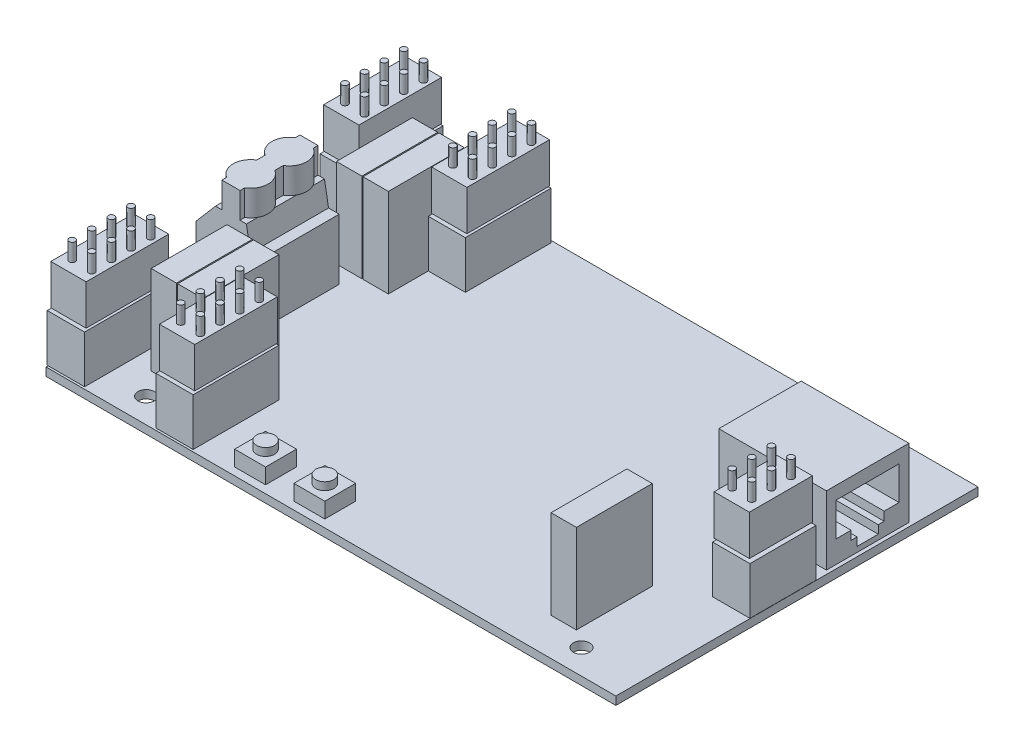
SolidWorks part; units mm, degrees
ref_plane "Front Plane" through (0, 0, 0) normal (0, 0, 1) x (1, 0, 0)
ref_plane "Top Plane" through (0, 0, 0) normal (0, 1, 0) x (1, 0, 0)
ref_plane "Right Plane" through (0, 0, 0) normal (1, 0, 0) x (0, 0, -1)
sketch "Sketch1" plane through (0, 0, 0) normal (0, 1, 0) x (1, 0, 0)
  line L0 (1.5775, 0) -> (0, 0) construction
  line L1 (-55.31, -35.15) -> (55.31, -35.15)
  line L2 (-55.31, -35.15) -> (-55.31, 35.15)
  line L3 (-55.31, 35.15) -> (55.31, 35.15)
  line L4 (55.31, -35.15) -> (55.31, 35.15)
  line L5 (-55.31, -35.15) -> (55.31, 35.15) construction
  line L6 (-55.31, 35.15) -> (55.31, -35.15) construction
  line L7 (-40.6725, -30.35) -> (43.8275, -30.35) construction
  line L8 (-40.6725, -30.35) -> (-40.6725, 30.35) construction
  line L9 (-40.6725, 30.35) -> (43.8275, 30.35) construction
  line L10 (43.8275, -30.35) -> (43.8275, 30.35) construction
  line L11 (-40.6725, -30.35) -> (43.8275, 30.35) construction
  line L12 (-40.6725, 30.35) -> (43.8275, -30.35) construction
  line L13 (-42.26, -30.35) -> (-55.31, -30.35) construction
  circle A0 centre (-40.6725, -30.35) radius 1.5875
  circle A1 centre (-40.6725, 30.35) radius 1.5875
  circle A2 centre (43.8275, 30.35) radius 1.5875
  circle A3 centre (43.8275, -30.35) radius 1.5875
  point P0 (0, 0)
  point P14 (0, 0)
  dimension "D3" = 3.175
  dimension "D6" = 4.8
  dimension "D7" = 70.3
  dimension "D1" = 13.05
  dimension "D2" = 110.62
  dimension "D4" = 84.5
  dimension "D5" = 60.7
extrude "Boss-Extrude1" add sketch "Sketch1" against normal blind 1.5875
sketch "Sketch2" plane through (0, 0, 0) normal (0, 1, 0) x (1, 0, 0)
  line L0 (-30.1535, -20.707) -> (-30.1535, -24.517) construction
  line L1 (-30.1535, -24.517) -> (-30.1535, -28.327) construction
  line L2 (-30.1535, -28.327) -> (-30.1535, -32.137) construction
  line L3 (51.0175, 1.137) -> (51.0175, -6.483) construction
  line L4 (51.0175, 1.137) -> (51.0175, -2.673) construction
  line L5 (-30.1535, 24.505) -> (-30.1535, 20.695) construction
  line L6 (-30.1535, 32.125) -> (-30.1535, 28.315) construction
  line L7 (-30.1535, 28.315) -> (-30.1535, 24.505) construction
  line L8 (-51.1085, 28.315) -> (-51.1085, 24.505) construction
  line L9 (-51.2355, -24.517) -> (-51.2355, -28.327) construction
  line L10 (-51.1085, 24.505) -> (-51.1085, 20.695) construction
  line L11 (-51.2355, -28.327) -> (-51.2355, -32.137) construction
  line L12 (-51.1085, 32.125) -> (-51.1085, 28.315) construction
  line L13 (-51.2355, -20.707) -> (-51.2355, -24.517) construction
  line L17 (55.31, 35.15) -> (-55.31, 35.15) construction
  line L19 (-55.1725, -34.55) -> (54.8275, -34.55) construction
  line L20 (-55.1725, -34.55) -> (-55.1725, 34.55) construction
  line L21 (-55.1725, 34.55) -> (54.8275, 34.55) construction
  line L22 (54.8275, -34.55) -> (54.8275, 34.55) construction
  circle A0 centre (51.0175, 1.137) radius 0.5
  circle A1 centre (51.0175, -2.673) radius 0.5
  circle A2 centre (51.0175, -6.483) radius 0.5
  circle A3 centre (-30.1535, -20.707) radius 0.5
  circle A4 centre (-30.1535, -24.517) radius 0.5
  circle A5 centre (-30.1535, -28.327) radius 0.5
  circle A6 centre (-30.1535, -32.137) radius 0.5
  circle A7 centre (-30.1535, 32.125) radius 0.5
  circle A8 centre (-30.1535, 20.695) radius 0.5
  circle A9 centre (-30.1535, 24.505) radius 0.5
  circle A10 centre (-30.1535, 28.315) radius 0.5
  circle A11 centre (-51.1085, 28.315) radius 0.5
  circle A12 centre (-51.1085, 24.505) radius 0.5
  circle A13 centre (-51.2355, -28.327) radius 0.5
  circle A14 centre (-51.2355, -20.707) radius 0.5
  circle A15 centre (-51.2355, -24.517) radius 0.5
  circle A16 centre (-51.1085, 32.125) radius 0.5
  circle A17 centre (-51.2355, -32.137) radius 0.5
  circle A18 centre (-51.1085, 20.695) radius 0.5
  circle A19 centre (-40.6725, -30.35) radius 1.5875 construction
  dimension "D1" = 3.937
  dimension "D2" = 14.5
  dimension "D3" = 1
  dimension "D4" = 25.019
  dimension "D5" = 3.81
  dimension "D6" = 4.064
  dimension "D7" = 14.455
  dimension "D8" = 25.019
  dimension "D9" = 69.1
  dimension "D11" = 13.843
  dimension "D10" = 66.675
  dimension "D12" = 4.2
  dimension "D15" = 35.687
  dimension "D13" = 110
  dimension "D14" = 3.81
extrude "Cut-Extrude1" cut sketch "Sketch2" against normal through all
sketch "Sketch3" plane through (0, 0, 0) normal (0, 1, 0) x (1, 0, 0)
  line L0 (55.31, 35.15) -> (-55.31, 35.15) construction
  line L1 (-44.42, -10.898) -> (-39.5, -10.898)
  line L2 (-44.42, -10.898) -> (-44.42, -25.63)
  line L3 (-44.42, -25.63) -> (-39.5, -25.63)
  line L4 (-39.5, -10.898) -> (-39.5, -25.63)
  line L5 (-44.42, -10.898) -> (-39.5, -25.63) construction
  line L6 (-44.42, -25.63) -> (-39.5, -10.898) construction
  line L11 (-39.27, -25.63) -> (-34.35, -25.63)
  line L12 (-39.27, -25.63) -> (-39.27, -10.898)
  line L13 (-39.27, -10.898) -> (-34.35, -10.898)
  line L14 (-34.35, -25.63) -> (-34.35, -10.898)
  line L15 (-39.27, -25.63) -> (-34.35, -10.898) construction
  line L16 (-39.27, -10.898) -> (-34.35, -25.63) construction
  line L17 (-39.27, 10.348) -> (-34.35, 10.348)
  line L18 (-39.27, 10.348) -> (-39.27, 25.08)
  line L19 (-39.27, 25.08) -> (-34.35, 25.08)
  line L20 (-34.35, 10.348) -> (-34.35, 25.08)
  line L21 (-39.27, 10.348) -> (-34.35, 25.08) construction
  line L22 (-39.27, 25.08) -> (-34.35, 10.348) construction
  line L23 (-44.42, 10.348) -> (-39.5, 10.348)
  line L24 (-44.42, 10.348) -> (-44.42, 25.08)
  line L25 (-44.42, 25.08) -> (-39.5, 25.08)
  line L26 (-39.5, 10.348) -> (-39.5, 25.08)
  line L27 (-44.42, 10.348) -> (-39.5, 25.08) construction
  line L28 (-44.42, 25.08) -> (-39.5, 10.348) construction
  line L29 (55.31, -35.15) -> (55.31, 35.15) construction
  line L32 (35.46, -13.148) -> (40.38, -13.148)
  line L33 (35.46, -13.148) -> (35.46, -27.88)
  line L34 (35.46, -27.88) -> (40.38, -27.88)
  line L35 (40.38, -13.148) -> (40.38, -27.88)
  line L36 (35.46, -13.148) -> (40.38, -27.88) construction
  line L37 (35.46, -27.88) -> (40.38, -13.148) construction
  line L38 (-55.31, -35.15) -> (55.31, -35.15) construction
  line L39 (-55.31, 35.15) -> (-55.31, -35.15) construction
  point P0 (-41.96, -18.264)
  point P5 (-36.81, -18.264)
  point P10 (-36.81, 17.714)
  point P15 (-41.96, 17.714)
  point P28 (37.92, -20.514)
  dimension "D1" = 14.732
  dimension "D2" = 10.07
  dimension "D3" = 9.52
  dimension "D4" = 4.92
  dimension "D5" = 10.89
  dimension "D6" = 10.07
  dimension "D7" = 7.27
  dimension "D8" = 50.71
  dimension "D9" = 14.93
  dimension "D10" = 19.85
extrude "Boss-Extrude2" add sketch "Sketch3" along normal blind 17.25
sketch "Sketch4" plane through (0, 0, 0) normal (0, 1, 0) x (1, 0, 0)
  line L0 (55.31, 35.15) -> (-55.31, 35.15) construction
  line L1 (-53.44, -7.95) -> (-40.74, -7.95)
  line L2 (-53.44, -7.95) -> (-53.44, 7.2)
  line L3 (-53.44, 7.2) -> (-40.74, 7.2)
  line L4 (-40.74, -7.95) -> (-40.74, 7.2)
  line L5 (-53.44, -7.95) -> (-40.74, 7.2) construction
  line L6 (-53.44, 7.2) -> (-40.74, -7.95) construction
  line L7 (-55.31, 35.15) -> (-55.31, -35.15) construction
  line L8 (-55.31, -35.15) -> (55.31, -35.15) construction
  point P0 (-47.09, -0.375)
  dimension "D1" = 15.15
  dimension "D2" = 12.7
  dimension "D3" = 1.87
  dimension "D4" = 27.95
  dimension "D5" = 27.2
extrude "Boss-Extrude3" add sketch "Sketch4" along normal blind 11.8
sketch "Sketch5" plane through (0, 0, 7.95) normal (0, 0, 1) x (1, 0, 0)
  line L0 (-53.44, 11.8) -> (-40.74, 11.8) construction
  line L1 (-53.44, 11.8) -> (-42.81, 11.8)
  line L2 (-53.44, 11.8) -> (-49.6035, 16.3)
  line L3 (-49.6035, 16.3) -> (-43.6035, 16.3)
  line L4 (-43.6035, 16.3) -> (-42.81, 11.8)
  line L6 (-40.74, 11.8) -> (-40.74, 0) construction
  line L8 (-53.44, 0) -> (-40.74, 0) construction
  dimension "D1" = 16.3
  dimension "D2" = 2.07
  dimension "D3" = 100
  dimension "D4" = 6
extrude "Boss-Extrude4" add sketch "Sketch5" against normal up to surface (15.15 mm away) up to face at (-47.09, 5.9, -7.2)
sketch "Sketch6" plane through (0, 16.3, 0) normal (0, 1, 0) x (1, 0, 0)
  line L0 (-49.6035, 7.2) -> (-43.6035, 7.2) construction
  line L1 (-48.3535, 7.2) -> (-44.8535, 7.2)
  line L2 (-48.3535, 7.2) -> (-48.3535, 6.29)
  line L3 (-48.3535, -7.95) -> (-44.8535, -7.95)
  line L4 (-44.8535, 7.2) -> (-44.8535, 6.29)
  line L5 (-43.6035, -7.95) -> (-49.6035, -7.95) construction
  line L6 (-46.6035, 3.375) -> (-46.6035, -4.125) construction
  line L7 (-44.8535, -0.375) -> (-48.3535, -0.375) construction
  line L8 (-48.3535, -7.04) -> (-48.3535, -7.95)
  line L9 (-48.3535, 0.46) -> (-48.3535, -1.21)
  line L10 (-44.8535, 0.46) -> (-44.8535, -1.21)
  line L11 (-44.8535, -7.04) -> (-44.8535, -7.95)
  arc A0 (-48.3535, -1.21) -> (-48.3535, -7.04) centre (-46.6035, -4.125) ccw
  arc A1 (-44.8535, 0.46) -> (-44.8535, 6.29) centre (-46.6035, 3.375) ccw
  arc A2 (-48.3535, 6.29) -> (-48.3535, 0.46) centre (-46.6035, 3.375) ccw
  arc A3 (-44.8535, -7.04) -> (-44.8535, -1.21) centre (-46.6035, -4.125) ccw
  point P8 (-46.6035, -7.95)
  point P15 (-46.6035, -0.375)
  dimension "D2" = 6.8
  dimension "D3" = 7.5
  dimension "D1" = 3.5
extrude "Boss-Extrude5" add sketch "Sketch6" along normal blind 5
sketch "Sketch7" plane through (0, 0, 0) normal (0, 1, 0) x (1, 0, 0)
  line L0 (55.31, 35.15) -> (-55.31, 35.15) construction
  line L1 (33.69, 6.45) -> (54.59, 6.45)
  line L2 (33.69, 6.45) -> (33.69, 22.45)
  line L3 (33.69, 22.45) -> (54.59, 22.45)
  line L4 (54.59, 6.45) -> (54.59, 22.45)
  line L5 (55.31, -35.15) -> (55.31, 35.15) construction
  dimension "D1" = 12.7
  dimension "D2" = 0.72
  dimension "D3" = 16
  dimension "D4" = 20.9
extrude "Boss-Extrude6" add sketch "Sketch7" along normal blind 13.33
sketch "Sketch8" plane through (54.59, 0, 0) normal (1, 0, 0) x (0, 0, -1)
  line L0 (16.51, 2.6125) -> (17.66, 2.6125)
  line L1 (8.35, 10.83) -> (20.55, 10.83)
  line L2 (8.35, 10.83) -> (8.35, 4.3125)
  line L3 (8.35, 4.3125) -> (11.24, 4.3125)
  line L4 (20.55, 10.83) -> (20.55, 4.3125)
  line L6 (11.24, 4.3125) -> (11.24, 2.6125)
  line L7 (11.24, 2.6125) -> (12.39, 2.6125)
  line L8 (17.66, 4.3125) -> (17.66, 2.6125)
  line L10 (12.39, 2.6125) -> (12.39, 1.0125)
  line L11 (12.39, 1.0125) -> (16.51, 1.0125)
  line L12 (16.51, 2.6125) -> (16.51, 1.0125)
  line L13 (17.66, 4.3125) -> (20.55, 4.3125)
  line L14 (14.45, 10.83) -> (14.45, 13.33) construction
  line L15 (6.45, 13.33) -> (22.45, 13.33) construction
  line L16 (6.45, 13.33) -> (6.45, 0) construction
  line L17 (-35.15, -1.5875) -> (35.15, -1.5875) construction
  dimension "D1" = 1.9
  dimension "D2" = 2.5
  dimension "D3" = 2.6
  dimension "D4" = 4.2
  dimension "D5" = 5.9
  dimension "D6" = 6.42
  dimension "D7" = 4.12
extrude "Cut-Extrude2" cut sketch "Sketch8" against normal blind 10.5
sketch "Sketch9" plane through (0, 0, 0) normal (0, 1, 0) x (1, 0, 0)
  line L0 (-55.31, -35.15) -> (55.31, -35.15) construction
  line L1 (-20.19, -27.65) -> (-14.19, -27.65)
  line L2 (-20.19, -27.65) -> (-20.19, -33.65)
  line L3 (-20.19, -33.65) -> (-14.19, -33.65)
  line L4 (-14.19, -27.65) -> (-14.19, -33.65)
  line L5 (-8.69, -27.65) -> (-2.69, -27.65)
  line L6 (-8.69, -27.65) -> (-8.69, -33.65)
  line L7 (-8.69, -33.65) -> (-2.69, -33.65)
  line L8 (-2.69, -27.65) -> (-2.69, -33.65)
  line L9 (55.31, -35.15) -> (55.31, 35.15) construction
  dimension "D1" = 6
  dimension "D2" = 1.5
  dimension "D3" = 17.5
  dimension "D4" = 58
extrude "Boss-Extrude7" add sketch "Sketch9" along normal blind 3
sketch "Sketch10" plane through (0, 3, 0) normal (0, 1, 0) x (1, 0, 0)
  line L0 (-14.19, -27.65) -> (-20.19, -33.65) construction
  line L1 (-2.69, -27.65) -> (-8.69, -33.65) construction
  circle A0 centre (-17.19, -30.65) radius 1.75
  circle A1 centre (-5.69, -30.65) radius 1.75
  dimension "D1" = 3.5
extrude "Boss-Extrude8" add sketch "Sketch10" along normal blind 1.5
sketch "Sketch11" plane through (0, 0, 0) normal (0, 1, 0) x (1, 0, 0)
  line L0 (-30.1535, -20.707) -> (-30.1535, -18.107) construction
  line L1 (-34.4035, 34.725) -> (-27.1535, 34.725)
  line L2 (-34.4035, 34.725) -> (-34.4035, 18.095)
  line L3 (-34.4035, 18.095) -> (-27.1535, 18.095)
  line L4 (-27.1535, 34.725) -> (-27.1535, 18.095)
  line L5 (-55.3585, 34.725) -> (-48.1085, 34.725)
  line L6 (-55.3585, 34.725) -> (-55.3585, 18.095)
  line L7 (-55.3585, 18.095) -> (-48.1085, 18.095)
  line L8 (-48.1085, 34.725) -> (-48.1085, 18.095)
  line L9 (-55.4855, -18.107) -> (-48.2355, -18.107)
  line L10 (-55.4855, -18.107) -> (-55.4855, -34.737)
  line L11 (-55.4855, -34.737) -> (-48.2355, -34.737)
  line L12 (-48.2355, -18.107) -> (-48.2355, -34.737)
  line L13 (-34.4035, -18.107) -> (-27.1535, -18.107)
  line L14 (-34.4035, -18.107) -> (-34.4035, -34.737)
  line L15 (-34.4035, -34.737) -> (-27.1535, -34.737)
  line L16 (-27.1535, -18.107) -> (-27.1535, -34.737)
  line L17 (48.0175, 3.737) -> (55.2675, 3.737)
  line L18 (48.0175, 3.737) -> (48.0175, -9.083)
  line L19 (48.0175, -9.083) -> (55.2675, -9.083)
  line L20 (55.2675, 3.737) -> (55.2675, -9.083)
  line L21 (-30.1535, -20.707) -> (-34.4035, -20.707) construction
  line L22 (-51.2355, -20.707) -> (-55.4855, -20.707) construction
  line L23 (-51.1085, 32.125) -> (-55.3585, 32.125) construction
  line L24 (-30.1535, 32.125) -> (-34.4035, 32.125) construction
  line L25 (-51.2355, -18.107) -> (-51.2355, -20.707) construction
  line L26 (-51.1085, 34.725) -> (-51.1085, 32.125) construction
  line L27 (-30.1535, 34.725) -> (-30.1535, 32.125) construction
  line L28 (-30.1535, 20.695) -> (-30.1535, 18.095) construction
  line L29 (-30.1535, -32.137) -> (-30.1535, -34.737) construction
  line L30 (51.0175, 1.137) -> (51.0175, 3.737) construction
  line L31 (51.0175, -6.483) -> (51.0175, -9.083) construction
  line L32 (51.0175, -6.483) -> (55.2675, -6.483) construction
  circle A0 centre (-30.1535, 32.125) radius 0.5 construction
  circle A1 centre (-51.1085, 32.125) radius 0.5 construction
  dimension "D3" = 3
  dimension "D1" = 7.25
  dimension "D2" = 2.6
extrude "Boss-Extrude9" add sketch "Sketch11" along normal blind 9.2
sketch "Sketch12" plane through (0, 9.2, 0) normal (0, 1, 0) x (1, 0, 0)
  line L0 (-55.0855, -26.422) -> (-55.4855, -26.422) construction
  line L1 (-55.0855, -18.407) -> (-48.2355, -18.407)
  line L2 (-55.0855, -18.407) -> (-55.0855, -34.437)
  line L3 (-55.0855, -34.437) -> (-48.2355, -34.437)
  line L4 (-48.2355, -18.407) -> (-48.2355, -34.437)
  line L5 (-55.4855, -18.107) -> (-55.4855, -34.737) construction
  line L6 (-48.2355, -34.737) -> (-48.2355, -18.107) construction
  line L7 (-54.9585, 18.395) -> (-48.1085, 18.395)
  line L8 (-54.9585, 18.395) -> (-54.9585, 34.425)
  line L9 (-54.9585, 26.41) -> (-55.3585, 26.41) construction
  line L10 (-48.1085, 18.395) -> (-48.1085, 34.425)
  line L11 (-54.9585, 34.425) -> (-48.1085, 34.425)
  line L12 (-55.3585, 34.725) -> (-55.3585, 18.095) construction
  line L13 (-34.0035, -34.437) -> (-27.1535, -34.437)
  line L14 (-34.0035, 18.395) -> (-34.0035, 34.425)
  line L15 (-27.1535, -18.407) -> (-27.1535, -34.437)
  line L16 (-34.0035, 18.395) -> (-27.1535, 18.395)
  line L17 (-27.1535, 18.395) -> (-27.1535, 34.425)
  line L18 (-34.0035, 26.41) -> (-34.4035, 26.41) construction
  line L19 (-34.0035, 34.425) -> (-27.1535, 34.425)
  line L20 (-34.0035, -26.422) -> (-34.4035, -26.422) construction
  line L21 (-34.0035, -18.407) -> (-34.0035, -34.437)
  line L22 (-34.0035, -18.407) -> (-27.1535, -18.407)
  line L23 (-34.4035, -25.63) -> (-34.4035, -34.737) construction
  line L24 (-34.4035, 34.725) -> (-34.4035, 25.08) construction
  line L25 (48.0175, -8.783) -> (48.0175, 3.437)
  line L26 (48.0175, 3.437) -> (54.8675, 3.437)
  line L27 (54.8675, -2.673) -> (55.2675, -2.673) construction
  line L28 (48.0175, -8.783) -> (54.8675, -8.783)
  line L29 (54.8675, -8.783) -> (54.8675, 3.437)
  line L33 (55.2675, -9.083) -> (55.2675, 3.737) construction
  dimension "D1" = 16.03
  dimension "D2" = 6.85
  dimension "D3" = 12.22
extrude "Boss-Extrude10" add sketch "Sketch12" along normal offset from surface (7.8 mm away) 17.5 from offset 0.5 separate body up to face at (-33.7943, 0, 22.343) offset beyond the face yes
sketch "Sketch13" plane through (0, 17.5, 0) normal (0, 1, 0) x (1, 0, 0)
  line L0 (-28.3535, 34.425) -> (-28.3535, 32.125) construction
  line L1 (-34.0035, 34.425) -> (-27.1535, 34.425) construction
  line L2 (-28.3535, 32.125) -> (-27.1535, 32.125) construction
  line L3 (-27.1535, 34.425) -> (-27.1535, 18.395) construction
  line L4 (-49.3085, 34.425) -> (-49.3085, 32.125) construction
  line L5 (-54.9585, 34.425) -> (-48.1085, 34.425) construction
  line L6 (-49.3085, 32.125) -> (-48.1085, 32.125) construction
  line L7 (-48.1085, 34.425) -> (-48.1085, 18.395) construction
  line L8 (-49.4355, -18.407) -> (-49.4355, -20.707) construction
  line L9 (-55.0855, -18.407) -> (-48.2355, -18.407) construction
  line L10 (-49.4355, -20.707) -> (-48.2355, -20.707) construction
  line L11 (-48.2355, -18.407) -> (-48.2355, -34.437) construction
  line L12 (-28.3535, -18.407) -> (-28.3535, -20.707) construction
  line L13 (-34.0035, -18.407) -> (-27.1535, -18.407) construction
  line L14 (-28.3535, -20.707) -> (-27.1535, -20.707) construction
  line L15 (-27.1535, -18.407) -> (-27.1535, -34.437) construction
  line L16 (48.0175, -6.483) -> (49.2175, -6.483) construction
  line L17 (49.2175, -6.483) -> (53.0275, -6.483) construction
  line L18 (48.0175, 3.737) -> (48.0175, -9.083) construction
  line L19 (49.2175, 1.137) -> (49.2175, 3.437) construction
  line L20 (49.2175, -6.483) -> (49.2175, -8.783) construction
  line L21 (54.8675, -8.783) -> (48.0175, -8.783) construction
  line L22 (-49.3085, 32.125) -> (-53.1185, 32.125) construction
  line L23 (-28.3535, 20.695) -> (-28.3535, 18.395) construction
  line L24 (-27.1535, 18.395) -> (-34.0035, 18.395) construction
  line L25 (48.0175, 3.437) -> (54.8675, 3.437) construction
  circle A0 centre (-49.4355, -20.707) radius 0.6
  circle A1 centre (-28.3535, -20.707) radius 0.6
  circle A2 centre (-28.3535, 32.125) radius 0.6
  circle A3 centre (-49.3085, 32.125) radius 0.6
  circle A5 centre (49.2175, -6.483) radius 0.6
  circle A6 centre (-53.1185, 32.125) radius 0.6
  circle A7 centre (-32.1635, 32.125) radius 0.6
  circle A8 centre (-53.2455, -20.707) radius 0.6
  circle A9 centre (-32.1635, -20.707) radius 0.6
  circle A10 centre (-53.1185, 28.315) radius 0.6
  circle A11 centre (-32.1635, 28.315) radius 0.6
  circle A12 centre (-53.2455, -24.517) radius 0.6
  circle A13 centre (-32.1635, -24.517) radius 0.6
  circle A14 centre (-53.1185, 24.505) radius 0.6
  circle A15 centre (-32.1635, 24.505) radius 0.6
  circle A16 centre (-53.2455, -28.327) radius 0.6
  circle A17 centre (-32.1635, -28.327) radius 0.6
  circle A18 centre (-53.1185, 20.695) radius 0.6
  circle A19 centre (-32.1635, 20.695) radius 0.6
  circle A20 centre (-53.2455, -32.137) radius 0.6
  circle A21 centre (-32.1635, -32.137) radius 0.6
  circle A22 centre (-49.3085, 28.315) radius 0.6
  circle A23 centre (-28.3535, 28.315) radius 0.6
  circle A24 centre (-49.4355, -24.517) radius 0.6
  circle A25 centre (-28.3535, -24.517) radius 0.6
  circle A26 centre (-49.3085, 24.505) radius 0.6
  circle A27 centre (-28.3535, 24.505) radius 0.6
  circle A28 centre (-49.4355, -28.327) radius 0.6
  circle A29 centre (-28.3535, -28.327) radius 0.6
  circle A30 centre (-49.3085, 20.695) radius 0.6
  circle A31 centre (-28.3535, 20.695) radius 0.6
  circle A32 centre (-49.4355, -32.137) radius 0.6
  circle A33 centre (-28.3535, -32.137) radius 0.6
  circle A34 centre (53.0275, -6.483) radius 0.6
  circle A35 centre (53.0275, -2.673) radius 0.6
  circle A36 centre (53.0275, 1.137) radius 0.6
  circle A37 centre (49.2175, -2.673) radius 0.6
  circle A38 centre (49.2175, 1.137) radius 0.6
  dimension "D1" = 1.2
  dimension "D3" = 2.3
  dimension "D2" = 1.2
  dimension "D6" = 3.81
  dimension "D9" = 3.81
  dimension "D4" = 2
  dimension "D5" = 4
  dimension "D7" = 2
  dimension "D8" = 3
extrude "Boss-Extrude11" add sketch "Sketch13" along normal blind 3.4
